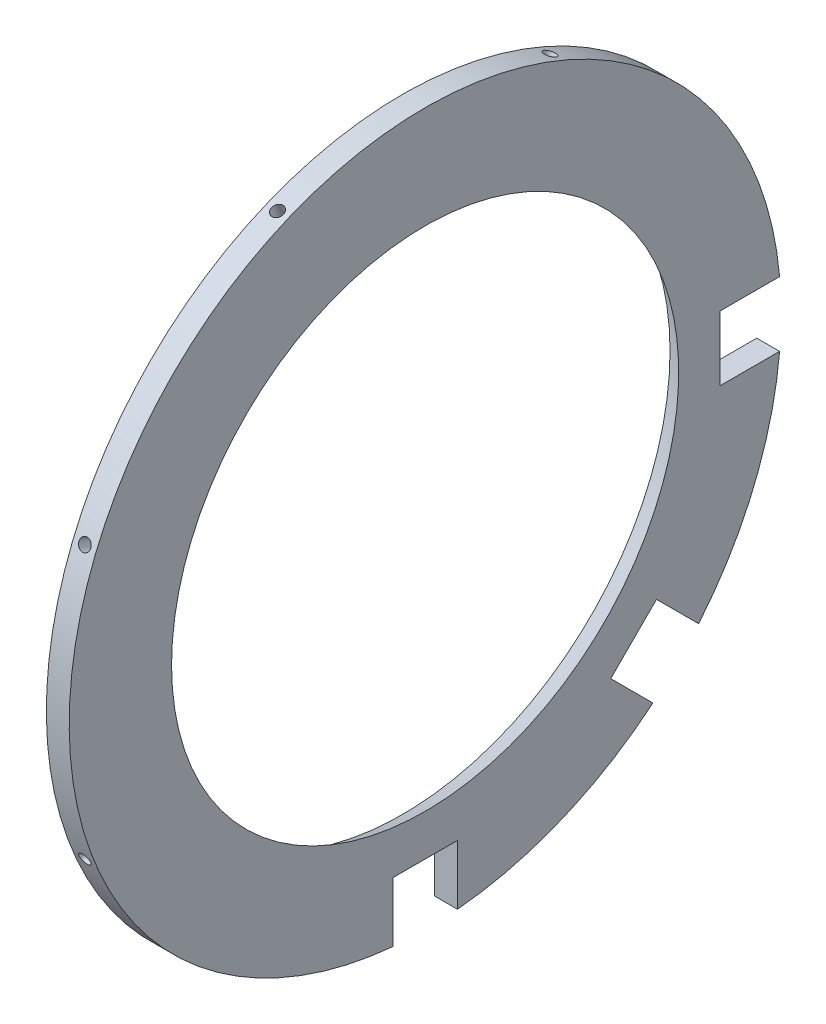
SolidWorks part; units mm, degrees
ref_plane "Front Plane" through (0, 0, 0) normal (0, 0, 1) x (1, 0, 0)
ref_plane "Top Plane" through (0, 0, 0) normal (0, 1, 0) x (1, 0, 0)
ref_plane "Right Plane" through (0, 0, 0) normal (1, 0, 0) x (0, 0, -1)
sketch "Ring Sketch" plane through (0, 0, 0) normal (0, 0, 1) x (1, 0, 0)
  line L0 (-300, 0) -> (300, 0) construction
  line L1 (3.175, 70.5315) -> (3.175, 99)
  line L2 (3.175, 99) -> (-3.175, 99)
  line L3 (-3.175, 99) -> (-3.175, 74.4685)
  line L4 (-3.175, 74.4685) -> (3.175, 70.5315)
revolve "Ring" add sketch "Ring Sketch" angle 360 about L0
ref_axis "Engine Axis" through (3.4925, 0, 0) along (-1, 0, 0)
sketch "Notch 180 Sketch" plane through (0, 0, 0) normal (1, 0, 0) x (0, 0, -1)
  line L0 (-9, -82) -> (9, -82)
  line L1 (9, -82) -> (9, -101)
  line L2 (9, -101) -> (-9, -101)
  line L3 (-9, -101) -> (-9, -82)
extrude "Notch 180" cut sketch "Notch 180 Sketch" against normal mid plane 8.35
sketch "Notch 225 Sketch" plane through (0, 0, 0) normal (1, 0, 0) x (0, 0, -1)
  line L0 (51.6188, -64.3467) -> (64.3467, -51.6188)
  line L1 (64.3467, -51.6188) -> (77.7817, -65.0538)
  line L2 (77.7817, -65.0538) -> (65.0538, -77.7817)
  line L3 (65.0538, -77.7817) -> (51.6188, -64.3467)
extrude "Notch 225" cut sketch "Notch 225 Sketch" against normal mid plane 8.35
sketch "Notch 270 Sketch" plane through (0, 0, 0) normal (1, 0, 0) x (0, 0, -1)
  line L0 (82, -9) -> (82, 9)
  line L1 (82, 9) -> (101, 9)
  line L2 (101, 9) -> (101, -9)
  line L3 (101, -9) -> (82, -9)
extrude "Notch 270" cut sketch "Notch 270 Sketch" against normal mid plane 8.35
ref_plane "Screw Hole Plane" through (0, 0, 0) normal (0, -0.3827, 0.9239) x (-1, 0, 0)
sketch "Screw Hole Sketch" plane through (0, 0, 0) normal (0, -0.3827, 0.9239) x (-1, 0, 0)
  line L0 (0, -88) -> (0, -103) construction
  line L1 (0, -91) -> (-1.65, -91)
  line L2 (-1.65, -91) -> (-1.65, -100)
  line L3 (-1.65, -100) -> (0, -100)
  line L4 (0, -100) -> (0, -91)
revolve "Screw Hole" cut sketch "Screw Hole Sketch" angle 360 about L0
pattern_circular "Screw Holes x8" count 8 over 360 about axis through (3.4925, 0, 0) along (-1, 0, 0) of "Screw Hole"
